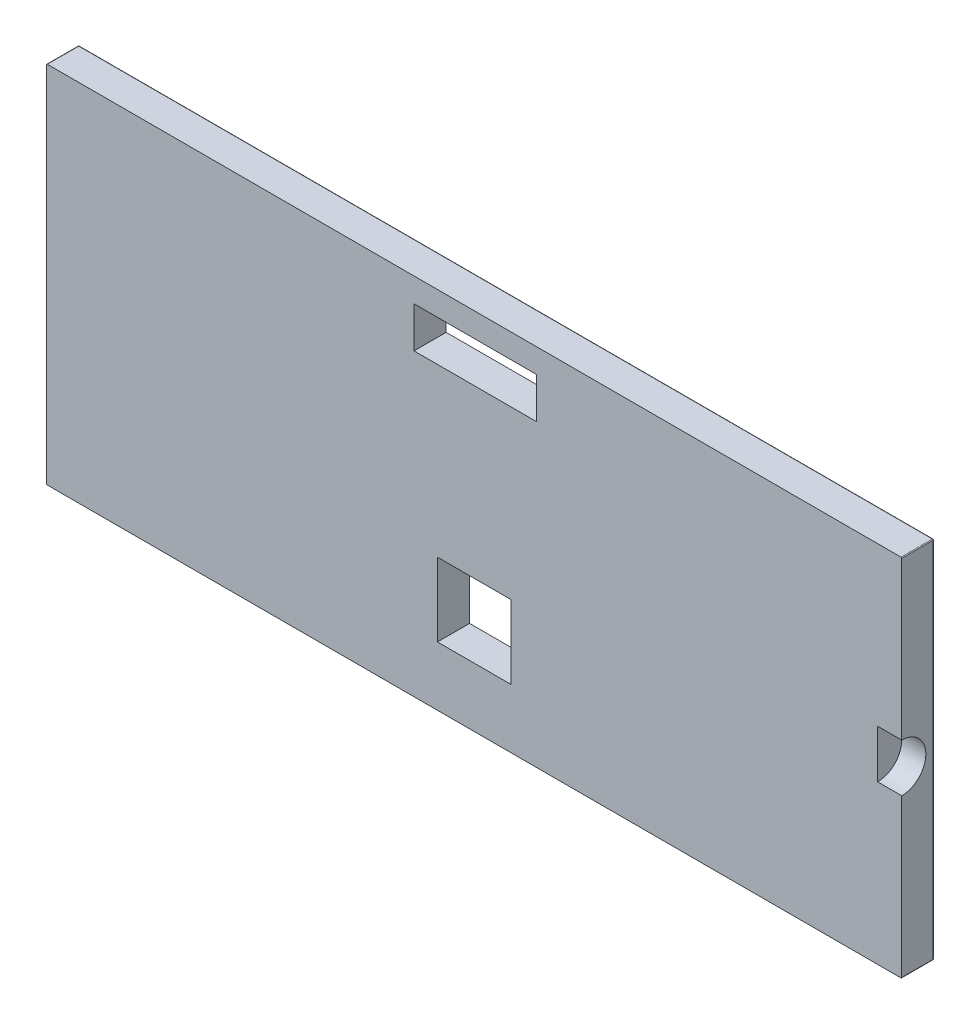
SolidWorks part; units mm, degrees
ref_plane "Front Plane" through (0, 0, 0) normal (0, 0, 1) x (1, 0, 0)
ref_plane "Top Plane" through (0, 0, 0) normal (0, 1, 0) x (1, 0, 0)
ref_plane "Right Plane" through (0, 0, 0) normal (1, 0, 0) x (0, 0, -1)
sketch "Sketch1" plane through (0, 0, 0) normal (0, 0, 1) x (1, 0, 0)
  line L1 (0, 0) -> (2704.084, 0)
  line L2 (0, 0) -> (0, 1152.398)
  line L3 (0, 1152.398) -> (2704.084, 1152.398)
  line L4 (2704.084, 0) -> (2704.084, 1152.398)
  line L5 (1161.796, 1076.198) -> (1548.892, 1076.198)
  line L6 (1161.796, 1076.198) -> (1161.796, 947.166)
  line L7 (1161.796, 947.166) -> (1548.892, 947.166)
  line L8 (1548.892, 1076.198) -> (1548.892, 947.166)
  line L9 (1235.9132, 187.1472) -> (1468.1708, 187.1472)
  line L10 (1235.9132, 187.1472) -> (1235.9132, 419.4048)
  line L11 (1235.9132, 419.4048) -> (1468.1708, 419.4048)
  line L12 (1468.1708, 187.1472) -> (1468.1708, 419.4048)
  line L13 (1235.9132, 187.1472) -> (1468.1708, 419.4048) construction
  line L14 (1235.9132, 419.4048) -> (1468.1708, 187.1472) construction
  point P9 (1352.042, 303.276)
  point P14 (0, 0)
  point P15 (1352.042, 0)
  dimension "D1" = 2704.084
  dimension "D2" = 1152.398
  dimension "D3" = 387.096
  dimension "D4" = 1161.796
  dimension "D5" = 129.032
  dimension "D6" = 76.2
  dimension "D7" = 232.2576
  dimension "D8" = 303.276
extrude "Boss-Extrude1" add sketch "Sketch1" along normal blind 76.2 and the other way blind 25.4
sketch "Sketch2" plane through (2704.084, 0, 0) normal (1, 0, 0) x (0, 0, -1)
  line L0 (-76.2, 0) -> (-76.2, 1152.398) construction
  circle A0 centre (-76.2, 576.199) radius 76.2
extrude "Cut-Extrude1" cut sketch "Sketch2" against normal blind 76.2
fillet "Fillet1" radius 2.54 8 edges at (1352.042, 0, -25.4) (2704.084, 576.199, -25.4) (1352.042, 1152.398, -25.4) (0, 576.199, -25.4) (0, 1152.398, 25.4) (0, 0, 25.4) (2704.084, 0, 25.4) (2704.084, 1152.398, 25.4)
